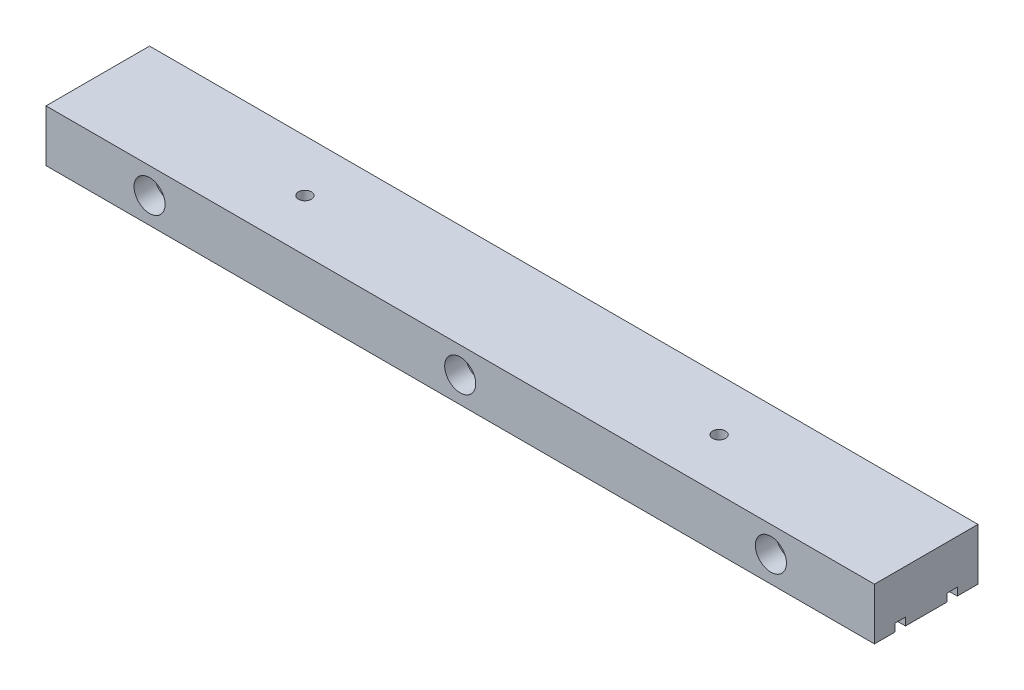
SolidWorks part; units mm, degrees
ref_plane "Ön Düzlem" through (0, 0, 0) normal (0, 0, 1) x (1, 0, 0)
ref_plane "Üst Düzlem" through (0, 0, 0) normal (0, 1, 0) x (1, 0, 0)
ref_plane "Sağ Düzlem" through (0, 0, 0) normal (1, 0, 0) x (0, 0, -1)
sketch "Çizim1" plane through (0, 0, 0) normal (0, 0, 1) x (1, 0, 0)
  line L1 (0, 0) -> (160, 0)
  line L2 (0, 0) -> (0, 10)
  line L3 (0, 10) -> (160, 10)
  line L4 (160, 0) -> (160, 10)
  dimension "D4" = 10
extrude "Yükseklik-Ekstrüzyon1" add sketch "Çizim1" along normal blind 20
sketch "Çizim4" plane through (0, 10, 0) normal (0, 1, 0) x (1, 0, 0)
  line L0 (0, -10) -> (160, -10) construction
  line L1 (0, -20) -> (0, 0) construction
  line L2 (160, -20) -> (160, 0) construction
  line L3 (40, 0) -> (40, -20) construction
  line L4 (160, 0) -> (0, 0) construction
  line L5 (160, -20) -> (0, -20) construction
  line L6 (120, 0) -> (120, -20) construction
  circle A0 centre (40, -10) radius 1.25
  circle A1 centre (120, -10) radius 1.25
  point P16 (40, -10)
  point P17 (120, -10)
  dimension "D1" = 40
  dimension "D2" = 40
sketch "Çizim6" plane through (0, 0, 0) normal (-1, 0, 0) x (0, 0, 1)
  line L0 (20, 0) -> (0, 0) construction
  line L1 (0, 10) -> (0, 0) construction
  line L2 (4, 0) -> (6, 0)
  line L3 (4, 0) -> (4, 1.5)
  line L4 (4, 1.5) -> (6, 1.5)
  line L5 (6, 0) -> (6, 1.5)
  line L6 (14, 0) -> (16, 0)
  line L7 (14, 0) -> (14, 1.5)
  line L8 (14, 1.5) -> (16, 1.5)
  line L9 (16, 0) -> (16, 1.5)
  line L10 (20, 10) -> (20, 0) construction
  dimension "D1" = 4
  dimension "D2" = 4
  dimension "D3" = 2
  dimension "D4" = 2
  dimension "D5" = 1.5
extrude "Kes-Ekstrüzyon1" cut sketch "Çizim6" against normal through all
sketch "Çizim7" plane through (0, 0, 0) normal (0, 0, -1) x (-1, 0, 0)
  line L0 (-160, 5) -> (0, 5) construction
  line L1 (-160, 0) -> (-160, 10) construction
  line L2 (0, 10) -> (0, 0) construction
  circle A0 centre (-140, 5) radius 1.25
  circle A1 centre (-80, 5) radius 1.25
  circle A2 centre (-20, 5) radius 1.25
  point P6 (-140, 5)
  point P7 (-80, 5)
  point P8 (-20, 5)
  dimension "D1" = 20
  dimension "D2" = 20
extrude "Cut-Extrude1" cut sketch "Çizim4" against normal through all
cosmetic thread "Cosmetic Thread1" parameters "D2"=3
cosmetic thread "Cosmetic Thread2" parameters "D2"=3
extrude "Cut-Extrude2" cut sketch "Çizim7" against normal through all
sketch "Sketch1" plane through (0, 0, 0) normal (0, 0, -1) x (-1, 0, 0)
  circle A0 centre (-140, 5) radius 3
  circle A1 centre (-80, 5) radius 3
  circle A2 centre (-20, 5) radius 3
extrude "Cut-Extrude3" cut sketch "Sketch1" against normal blind 4
cosmetic thread "Cosmetic Thread6" parameters "D2"=3
cosmetic thread "Cosmetic Thread7" parameters "D2"=3
cosmetic thread "Cosmetic Thread8" parameters "D2"=3
sketch "Sketch2" plane through (0, 0, 20) normal (0, 0, 1) x (1, 0, 0)
  line L0 (0, 10) -> (0, 0) construction
  circle A0 centre (20, 5) radius 3
  circle A1 centre (80, 5) radius 3
  circle A2 centre (140, 5) radius 3
extrude "Cut-Extrude4" cut sketch "Sketch2" against normal blind 4
cosmetic thread "Cosmetic Thread3" parameters "D2"=3
cosmetic thread "Cosmetic Thread4" parameters "D2"=3
cosmetic thread "Cosmetic Thread5" parameters "D2"=3
